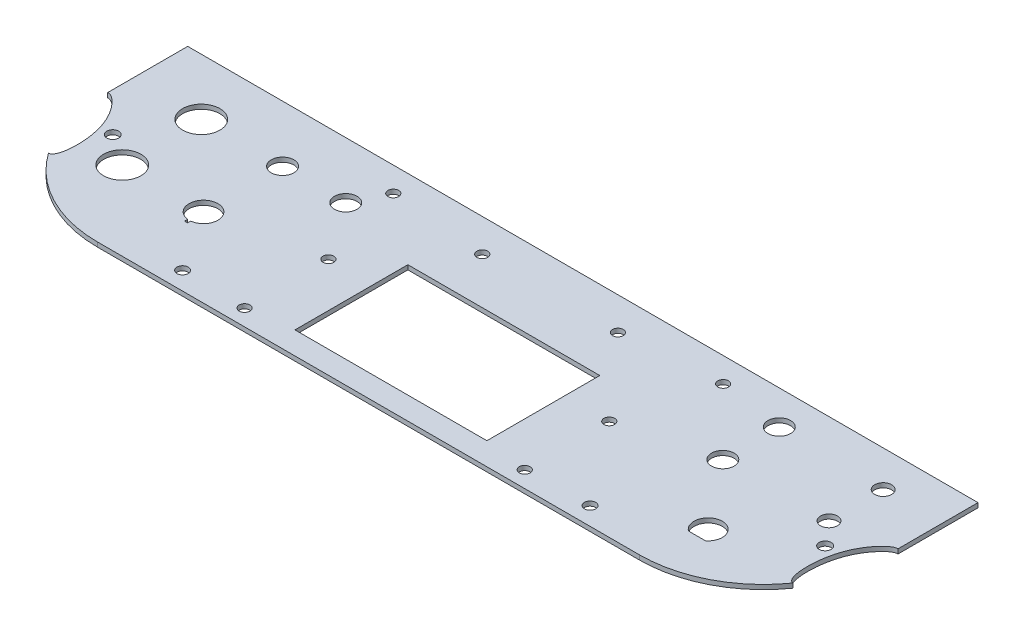
SolidWorks part; units mm, degrees
material "Thornel Mat VMA"
ref_plane "Front Plane" through (0, 0, 0) normal (0, 0, 1) x (1, 0, 0)
ref_plane "Top Plane" through (0, 0, 0) normal (0, 1, 0) x (1, 0, 0)
ref_plane "Right Plane" through (0, 0, 0) normal (1, 0, 0) x (0, 0, -1)
sketch "Sketch1" plane through (0, 0, 0) normal (0, 1, 0) x (1, 0, 0)
  line L13 (-222.25, 0) -> (222.25, 0) construction
  line L14 (222.25, -14.6125) -> (222.25, 36.1875)
  line L15 (222.25, 36.1875) -> (-222.25, 36.1875)
  line L16 (-222.25, -14.6125) -> (-222.25, 36.1875)
  line L18 (0, -95.4736) -> (0, 95.4736) construction
  line L19 (152.4, -84.4625) -> (-152.4, -84.4625)
  arc A0 (222.25, -14.6125) -> (152.4, -84.4625) centre (152.4, -14.6125) cw
  arc A1 (-152.4, -84.4625) -> (-222.25, -14.6125) centre (-152.4, -14.6125) cw
  point P10 (0, 0)
  point P16 (0, 0)
  point P17 (0, -84.4625)
  dimension "D1" = 50.8
  dimension "D2" = 444.5
  dimension "D3" = 304.8
  dimension "D5" = 120.65
  dimension "D6" = 36.1875
extrude "Boss-Extrude1" add sketch "Sketch1" along normal blind 2.54
sketch "Sketch2" plane through (0, 2.54, 0) normal (0, 1, 0) x (1, 0, 0)
  line L1 (53.975, -71.7625) -> (-53.975, -71.7625)
  line L2 (53.975, -71.7625) -> (53.975, -8.2625)
  line L3 (53.975, -8.2625) -> (-53.975, -8.2625)
  line L4 (-53.975, -71.7625) -> (-53.975, -8.2625)
  line L5 (53.975, -71.7625) -> (-53.975, -8.2625) construction
  line L6 (53.975, -8.2625) -> (-53.975, -71.7625) construction
  line L8 (-152.4, -84.4625) -> (152.4, -84.4625) construction
  point P0 (0, -40.0125)
  dimension "D1" = 63.5
  dimension "D2" = 12.7
  dimension "D3" = 107.95
extrude "Cut-Extrude1" cut sketch "Sketch2" against normal through all
sketch "Sketch4" plane through (0, 2.54, 0) normal (0, 1, 0) x (1, 0, 0)
  line L6 (-138.01, -48.0677) -> (-138.01, -49.8125)
  line L12 (-138.01, -49.8125) -> (-136.31, -49.8125)
  line L14 (-136.31, -49.8125) -> (-136.31, -48.0677)
  line L17 (222.25, -14.6125) -> (222.25, 36.1875) construction
  line L18 (222.25, 36.1875) -> (-222.25, 36.1875) construction
  line L19 (-222.25, 36.1875) -> (-222.25, -14.6125) construction
  line L21 (164.1475, -59.0625) -> (154.6225, -59.0625)
  line L22 (-152.4, -84.4625) -> (152.4, -84.4625) construction
  line L54 (87.5424, -0.6073) -> (87.4312, -0.6714)
  circle A0 centre (189.23, 15.8675) radius 4.7625
  circle A2 centre (-137.16, 4.4375) radius 6.35
  circle A3 centre (129.54, 17.1375) radius 6.35
  circle A4 centre (129.54, -14.6125) radius 6.35
  circle A6 centre (189.23, -14.6125) radius 4.7625
  circle A7 centre (-182.88, -40.0125) radius 10.5
  arc A8 (-136.31, -48.0677) -> (-138.01, -48.0677) centre (-137.16, -40.0125) ccw
  circle A9 centre (-182.88, 4.4375) radius 10.5
  arc A12 (164.1475, -59.0625) -> (154.6225, -59.0625) centre (159.385, -52.7125) ccw
  circle A25 centre (-101.6, 4.4375) radius 6.35
  circle A36 centre (-38.131, 17.7452) radius 3.025 construction
  circle A37 centre (-79, -27.9475) radius 3.025 construction
  circle A48 centre (-78.7827, -75.2875) radius 3.025 construction
  circle A49 centre (78.7827, -75.2875) radius 3.025 construction
  circle A51 centre (79, -27.9475) radius 3.025 construction
  arc A72 (85, -6.1987) -> (84.9641, -5.581) centre (79.666, -6.1987) ccw
  circle A73 centre (38.131, 17.7452) radius 3.025 construction
  circle A74 centre (-38.131, 17.7452) radius 3.025
  circle A75 centre (-79, -27.9475) radius 3.025
  circle A76 centre (-78.7827, -75.2875) radius 3.025
  circle A77 centre (78.7827, -75.2875) radius 3.025
  circle A78 centre (79, -27.9475) radius 3.025
  circle A79 centre (38.131, 17.7452) radius 3.025
  point P24 (-137.16, -49.8125)
  dimension "D2" = 12.7
  dimension "D3" = 15.875
  dimension "D11" = 9.8
  dimension "D12" = 16.2
  dimension "D20" = 31.75
  dimension "D25" = 9.525
  dimension "D10" = 21
  dimension "D4" = 31.75
  dimension "D5" = 20.32
  dimension "D6" = 33.02
  dimension "D7" = 59.69
  dimension "D8" = 35.56
  dimension "D9" = 50.8
  dimension "D13" = 39.37
  dimension "D14" = 85.09
  dimension "D15" = 62.865
  dimension "D16" = 31.75
  dimension "D17" = 76.2
  dimension "D18" = 6.35
  dimension "D19" = 1.7
  dimension "D21" = 31.75
sketch "Sketch5" plane through (0, 2.54, 0) normal (0, 1, 0) x (1, 0, 0)
  line L0 (222.25, -14.6125) -> (222.25, 36.1875) construction
  line L1 (0, -1.397) -> (0, 1.397) construction
  arc A0 (152.4, -84.4625) -> (222.25, -14.6125) centre (152.4, -14.6125) ccw construction
  spline S0 degree 3 poles (235.1366, 7.4285) (207.1804, -83.7935) (202.3049, -25.2668) (235.1366, 7.4285) (207.1804, -83.7935) (202.3049, -25.2668) knots -1 -0.674196 -0.483325 0 0.325804 0.516675 1 1.325804 1.516675 2 only from (209.4403, -54.9291) to (209.4403, -54.9291)
  spline S1 degree 3 poles (-235.1366, 7.4285) (-207.1804, -83.7935) (-202.3049, -25.2668) (-235.1366, 7.4285) (-207.1804, -83.7935) (-202.3049, -25.2668) knots -1 -0.674196 -0.483325 0 0.325804 0.516675 1 1.325804 1.516675 2 only from (-209.4403, -54.9291) to (-209.4403, -54.9291)
  line M8 (-222.25, 36.1875) -> (-222.25, -14.6125)
  arc M9 (-222.25, -14.6125) -> (-152.4, -84.4625) centre (-152.4, -14.6125) ccw
extrude "Cut-Extrude4" cut sketch "Sketch5" against normal up to surface (2.54 mm away) contours S1 M9 M8 | S0 region at (-213.6132, 2.54, 31.5069) up to face at (0, 0, 40.0125)
extrude "Cut-Extrude3" cut sketch "Sketch4" against normal through all contours A25 | A77 | A9 | A8 L6 L12 L14 | A7 | A6 | A0 | A3 | A2 | A12 L21 | A4 | A79 | A78 | A74 | A75 | A76 region at (-101.6, 2.54, -4.4375) region at (78.7827, 2.54, 75.2875)
sketch "Sketch6" plane through (0, 0, 0) normal (0, -1, 0) x (1, 0, 0)
  line L0 (0, -1.397) -> (0, 1.397) construction
  circle A0 centre (92.7683, -22.3351) radius 3.0138
  circle A1 centre (114.6033, 74.359) radius 3.1768
  circle A2 centre (200.3502, 27.8837) radius 3.3788
  circle A3 centre (-92.7683, -22.3351) radius 3.0138
  circle A4 centre (-200.3502, 27.8837) radius 3.3788
  circle A5 centre (-114.6033, 74.359) radius 3.1768
  circle A7 centre (-114.6033, 74.359) radius 3.325
  point P12 (0, 0)
  point P15 (-114.6033, 75.0989)
extrude "Cut-Extrude5" cut sketch "Sketch6" against normal through all contours A5 | A4 | A3 | A0 | A1 | A2 | A5 region at (92.7683, 0, -22.3351) region at (114.6033, 0, 74.359) region at (200.3502, 0, 27.8837) region at (-92.7683, 0, -22.3351) region at (-200.3502, 0, 27.8837) region at (-114.6033, 0, 74.359)
